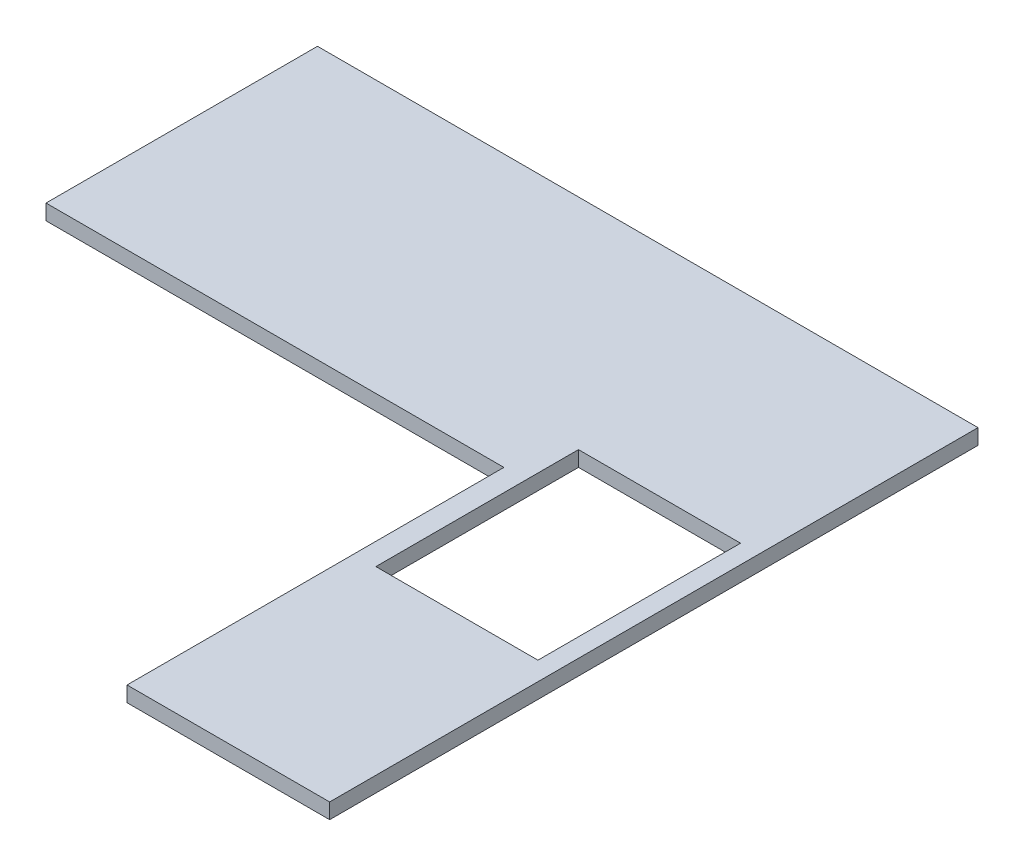
SolidWorks part; units mm, degrees
ref_plane "Спереди" through (0, 0, 0) normal (0, 0, 1) x (1, 0, 0)
ref_plane "Сверху" through (0, 0, 0) normal (0, 1, 0) x (1, 0, 0)
ref_plane "Справа" through (0, 0, 0) normal (1, 0, 0) x (0, 0, -1)
sketch "Эскиз1" plane through (0, 0, 0) normal (0, 1, 0) x (1, 0, 0)
  line L0 (0, 0) -> (0, 670)
  line L1 (0, 670) -> (1630, 670)
  line L2 (1630, 670) -> (1630, -930)
  line L3 (1630, -930) -> (1130, -930)
  line L4 (1130, -930) -> (1130, 0)
  line L5 (1130, 0) -> (0, 0)
  point P3 (0, 0)
extrude "Бобышка-Вытянуть1" add sketch "Эскиз1" along normal blind 38
sketch "Эскиз2" plane through (0, 38, 0) normal (0, 1, 0) x (1, 0, 0)
  line L1 (1184.0205, 130.03) -> (1584.0205, 130.03)
  line L2 (1184.0205, 130.03) -> (1184.0205, -369.97)
  line L3 (1184.0205, -369.97) -> (1584.0205, -369.97)
  line L4 (1584.0205, 130.03) -> (1584.0205, -369.97)
extrude "Вырез-Вытянуть1" cut sketch "Эскиз2" against normal through all
